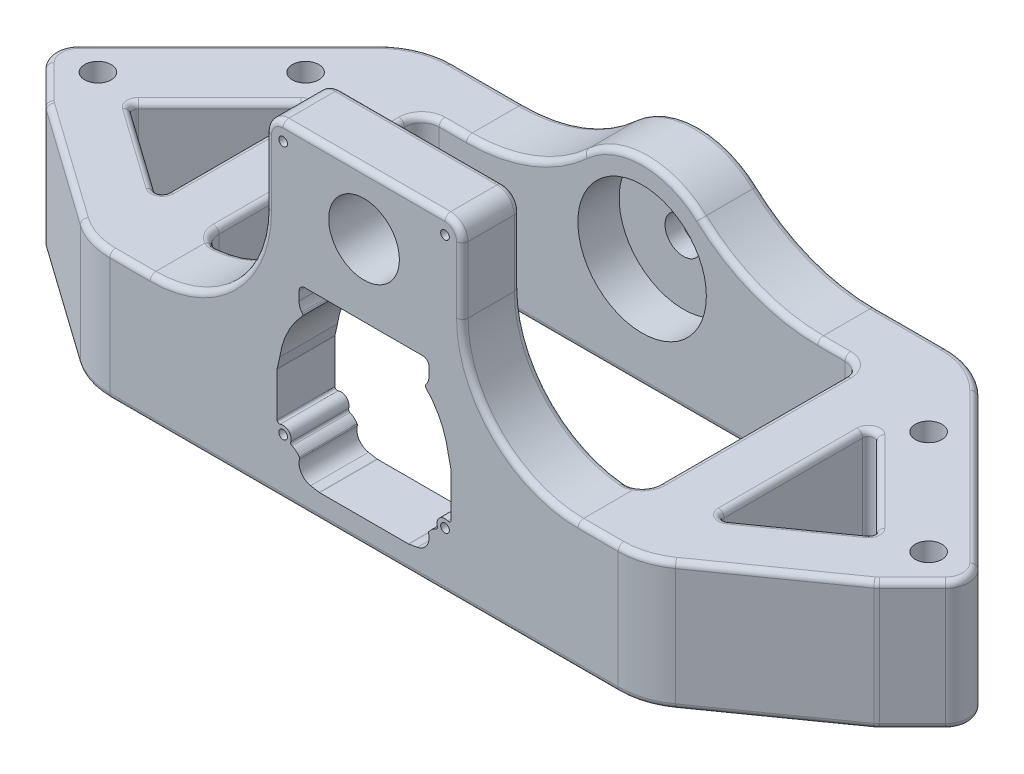
SolidWorks part; units mm, degrees
ref_plane "Front Plane" through (0, 0, 0) normal (0, 0, 1) x (1, 0, 0)
ref_plane "Top Plane" through (0, 0, 0) normal (0, 1, 0) x (1, 0, 0)
ref_plane "Right Plane" through (0, 0, 0) normal (1, 0, 0) x (0, 0, -1)
sketch "Sketch1" plane through (0, 0, 0) normal (0, 1, 0) x (1, 0, 0)
  line L0 (-48.1, -29.05) -> (-48.1, 29.05)
  line L1 (38.1, -19.05) -> (-38.1, -19.05)
  line L2 (38.1, -19.05) -> (38.1, 19.05)
  line L3 (38.1, 19.05) -> (-38.1, 19.05)
  line L4 (-38.1, -19.05) -> (-38.1, 19.05)
  line L5 (38.1, -19.05) -> (-38.1, 19.05) construction
  line L6 (38.1, 19.05) -> (-38.1, -19.05) construction
  line L11 (48.1, 29.05) -> (-48.1, 29.05)
  line L12 (48.1, -29.05) -> (48.1, 29.05)
  line L13 (48.1, -29.05) -> (-48.1, -29.05)
  line L14 (-48.1, 29.05) -> (-80.6068, -3.4568)
  line L15 (-80.6068, -3.4568) -> (-71.842, -12.2215)
  line L16 (-71.842, -12.2215) -> (-48.1, 11.5205)
  line L17 (0, 0) -> (0, 65.6417) construction
  line L18 (-76.3322, -7.7314) -> (0, 68.6008) construction
  line L19 (48.1, 29.05) -> (80.6068, -3.4568)
  line L20 (80.6068, -3.4568) -> (71.842, -12.2215)
  line L21 (71.842, -12.2215) -> (48.1, 11.5205)
  line L22 (-48.1, -29.05) -> (-71.842, -12.2215)
  line L23 (-48.1, -16.7927) -> (-64.669, -5.0485)
  line L24 (48.1, -29.05) -> (71.842, -12.2215)
  line L25 (48.1, -16.7927) -> (64.669, -5.0485)
  line L26 (-76.3322, -7.7314) -> (-269.4077, -200.8069) construction
  circle A0 centre (-71.842, -3.2413) radius 2.3
  circle A1 centre (-53.8815, 14.7193) radius 2.3
  circle A2 centre (53.8815, 14.7193) radius 2.3
  circle A3 centre (71.842, -3.2413) radius 2.3
  point P0 (0, 0)
  point P32 (-197.5656, -128.9648)
  point P34 (-215.5261, -146.9254)
  dimension "D10" = 4.6
  dimension "D1" = 10
  dimension "D2" = 45
  dimension "D3" = 12.3952
  dimension "D4" = 107.95
  dimension "D5" = 6.35
  dimension "D6" = 6.35
  dimension "D7" = 25.4
  dimension "D8" = 76.2
  dimension "D9" = 38.1
  dimension "D11" = 10
  dimension "D12" = 381
  dimension "D13" = 101.6
  dimension "D14" = 177.8
  dimension "D15" = 25.4
  dimension "D16" = 228.6
extrude "Boss-Extrude1" add sketch "Sketch1" along normal blind 22.25 contours L13 L12 L11 L0 L1 L4 L3 L2 | L15 L16 L0 L14 A1 A0 | L21 L20 L19 L12 A2 A3 | L0 L23 L16 L22 | L25 L12 L24 L21 region at (-58.2841, 0, 16.0663) region at (-46.9762, 0, 22.9214) region at (58.2841, 0, 16.0663) region at (-62.2337, 0, -6.6242) region at (62.2337, 0, -6.6242)
extrude "Boss-Extrude2" add sketch "Sketch1<3>" along normal blind 15.85 from surface contours L13 L12 L11 L0 L1 L4 L3 L2 region at (-46.9762, 0, 22.9214) starting at face at (53.623, 22.25, 3.4402)
sketch "Sketch1<3>" plane through (0, 0, 0) normal (0, 1, 0) x (1, 0, 0) same geometry as "Sketch1"
sketch "Sketch3" plane through (0, 0, 29.05) normal (0, 0, 1) x (1, 0, 0)
  line L0 (0, 0) -> (0, 38.1) construction
  line L1 (-48.1, 38.1) -> (48.1, 38.1) construction
  line L2 (7.7467, 4.2612) -> (9.2383, 4.5242)
  line L3 (-7.6773, 4.2551) -> (7.6773, 4.2551)
  line L4 (-9.2383, 4.5242) -> (-7.7467, 4.2612)
  line L5 (-15.0449, 19.0418) -> (-15.0449, 11.4779)
  line L6 (-14.5827, 21.1094) -> (-15.0348, 19.1309)
  line L7 (-10.7806, 29.7585) -> (-10.65, 29.5787)
  line L8 (-6.6626, 32.35) -> (-6.853, 32.6121)
  line L9 (6.853, 32.6121) -> (6.6626, 32.35)
  line L10 (10.65, 29.5787) -> (10.7806, 29.7585)
  line L11 (15.0348, 19.1309) -> (14.5827, 21.1094)
  line L12 (15.0449, 11.4779) -> (15.0449, 19.0418)
  line L13 (-48.1, 22.25) -> (-17, 22.25)
  line L14 (-17, 22.25) -> (-17, 56.7)
  line L15 (-17, 56.7) -> (17, 56.7)
  line L16 (17, 56.7) -> (17, 22.25)
  line L17 (17, 22.25) -> (48.1, 22.25)
  line L18 (48.1, 38.1) -> (48.1, 22.25) construction
  line L19 (48.1, 22.25) -> (48.1, 38.1)
  line L20 (48.1, 38.1) -> (17, 38.1)
  line L21 (-17, 38.1) -> (-48.1, 38.1)
  line L22 (-48.1, 38.1) -> (-48.1, 22.25)
  line L23 (-17, 38.1) -> (17, 38.1)
  line L24 (-11.2442, 31.1853) -> (-11.2442, 33.6774)
  line L25 (-11.2442, 33.6774) -> (11.1927, 33.6774)
  line L26 (11.1927, 33.6774) -> (11.2442, 31.1853)
  circle A0 centre (14, 9.8) radius 0.75
  circle A1 centre (-14, 9.8) radius 0.75
  circle A2 centre (-14, 53.7) radius 0.75
  circle A3 centre (14, 53.7) radius 0.75
  circle A4 centre (0, 46.05) radius 6.114
  arc A5 (12.4458, 8.8644) -> (11.1887, 7.8314) centre (13.5, 6.3) ccw
  arc A6 (9.2383, 4.5242) -> (11.1504, 7.5831) centre (8.8168, 6.9147) ccw
  arc A7 (7.6773, 4.2551) -> (7.7467, 4.2612) centre (7.6773, 4.6551) ccw
  arc A8 (-7.7467, 4.2612) -> (-7.6773, 4.2551) centre (-7.6773, 4.6551) ccw
  arc A9 (-11.1504, 7.5831) -> (-9.2383, 4.5242) centre (-8.8168, 6.9147) ccw
  arc A10 (-11.1887, 7.8314) -> (-12.4458, 8.8644) centre (-13.5, 6.3) ccw
  arc A11 (-12.6734, 9.3602) -> (-14.5014, 11.1045) centre (-14, 9.8) ccw
  arc A12 (-15.0348, 19.1309) -> (-15.0449, 19.0418) centre (-14.6449, 19.0418) ccw
  arc A13 (-10.6753, 29.1957) -> (-14.5827, 21.1094) centre (0, 19.05) ccw
  arc A14 (-6.853, 32.6121) -> (-10.7806, 29.7585) centre (-8.8168, 31.1853) ccw
  arc A15 (6.2909, 32.2555) -> (-6.2909, 32.2555) centre (0, 19.05) ccw
  arc A16 (10.7806, 29.7585) -> (6.853, 32.6121) centre (8.8168, 31.1853) ccw
  arc A17 (14.5827, 21.1094) -> (10.6753, 29.1957) centre (0, 19.05) ccw
  arc A18 (15.0449, 19.0418) -> (15.0348, 19.1309) centre (14.6449, 19.0418) ccw
  arc A19 (14.5014, 11.1045) -> (12.6734, 9.3602) centre (14, 9.8) ccw
  spline S0 degree 3 poles (12.4458, 8.8644) (12.5392, 8.9027) (12.6157, 8.9767) (12.699, 9.1584) (12.7052, 9.2644) (12.6734, 9.3602) knots 0 0 0 0 0.000302 0.000302 0.000604 0.000604 0.000604 0.000604 weights 1 1 1 1 1 1
  spline S1 degree 3 poles (11.1504, 7.5831) (11.1264, 7.6668) (11.1406, 7.7587) (11.1887, 7.8314) knots 0 0 0 0 0.000258 0.000258 0.000258 0.000258 weights 1 1 1 1
  spline S2 degree 3 poles (-11.1887, 7.8314) (-11.1406, 7.7587) (-11.1264, 7.6668) (-11.1504, 7.5831) knots 0 0 0 0 0.000258 0.000258 0.000258 0.000258 weights 1 1 1 1
  spline S3 degree 3 poles (-12.6734, 9.3602) (-12.7052, 9.2644) (-12.699, 9.1582) (-12.6155, 8.9765) (-12.5392, 8.9027) (-12.4458, 8.8644) knots 0 0 0 0 0.000302 0.000302 0.000604 0.000604 0.000604 0.000604 weights 1 1 1 1 1 1
  spline S4 degree 3 poles (-15.0449, 11.4779) (-15.0449, 11.3476) (-14.9779, 11.2213) (-14.7643, 11.0748) (-14.6231, 11.0578) (-14.5014, 11.1045) knots 0 0 0 0 0.000388 0.000388 0.000776 0.000776 0.000776 0.000776 weights 1 1 1 1 1 1
  spline S5 degree 3 poles (-10.65, 29.5787) (-10.6088, 29.522) (-10.5888, 29.4526) (-10.5979, 29.3131) (-10.627, 29.2466) (-10.6753, 29.1957) knots 0 0 0 0 0.000207 0.000207 0.000415 0.000415 0.000415 0.000415 weights 1 1 1 1 1 1
  spline S6 degree 3 poles (-6.2909, 32.2555) (-6.3541, 32.2254) (-6.4259, 32.2184) (-6.5613, 32.2528) (-6.6214, 32.2934) (-6.6626, 32.35) knots 0 0 0 0 0.000207 0.000207 0.000414 0.000414 0.000414 0.000414 weights 1 1 1 1 1 1
  spline S7 degree 3 poles (6.6626, 32.35) (6.6214, 32.2934) (6.5617, 32.2529) (6.4263, 32.2184) (6.3541, 32.2254) (6.2909, 32.2555) knots 0 0 0 0 0.000207 0.000207 0.000414 0.000414 0.000414 0.000414 weights 1 1 1 1 1 1
  spline S8 degree 3 poles (10.6753, 29.1957) (10.627, 29.2466) (10.598, 29.3127) (10.5887, 29.4522) (10.6088, 29.522) (10.65, 29.5787) knots 0 0 0 0 0.000207 0.000207 0.000415 0.000415 0.000415 0.000415 weights 1 1 1 1 1 1
  spline S9 degree 3 poles (14.5014, 11.1045) (14.6231, 11.0578) (14.765, 11.075) (14.9783, 11.2218) (15.0449, 11.3476) (15.0449, 11.4779) knots 0 0 0 0 0.000388 0.000388 0.000776 0.000776 0.000776 0.000776 weights 1 1 1 1 1 1
  point P5 (0, 19.05)
  point P17 (0, 19.05)
  point P86 (0, 33.6774)
  line M46 (48.1, 22.25) -> (48.1, 38.1)
  line M47 (48.1, 38.1) -> (-48.1, 38.1)
  line M48 (-48.1, 38.1) -> (-48.1, 22.25)
  dimension "D1" = 1.5
  dimension "D2" = 3
  dimension "D3" = 3
  dimension "D4" = 3
extrude "Boss-Extrude3" add sketch "Sketch3" against normal up to surface (10 mm away) contours L16 L15 L14 L23 A4 A3 A2 M47 region at (-16.6124, 47.4, 29.05) up to face at (0, 19.05, 19.05)
extrude "Cut-Extrude1" cut sketch "Sketch3<3>" against normal up to next contours L13 L14 M47 M48 | L16 L17 M46 M47 region at (-32.55, 30.175, 29.05) region at (32.55, 30.175, 29.05)
sketch "Sketch3<3>" plane through (0, 0, 29.05) normal (0, 0, 1) x (1, 0, 0) same geometry as "Sketch3"
extrude "Cut-Extrude2" cut sketch "Sketch3<4>" against normal up to next contours L3 L0 A15 S6 L8 A14 L7 S5 A13 L6 A12 L5 S4 A11 S3 A10 S2 A9 L4 A8 | L0 L3 A7 L2 A6 S1 A5 S0 A19 S9 L12 A18 L11 A17 S8 L10 A16 L9 S7 A15 | A1 | A0 | S6 A15 L25 L24 A14 L8 | S7 L9 A16 L26 L25 A15 region at (-6.6584, 18.6234, 29.05) region at (6.6584, 18.6234, 29.05) region at (-6.742, 33.2078, 29.05) region at (6.692, 33.2118, 29.05) region at (14, 9.8, 29.05) region at (-14, 9.8, 29.05)
sketch "Sketch3<4>" plane through (0, 0, 29.05) normal (0, 0, 1) x (1, 0, 0) same geometry as "Sketch3"
sketch "Sketch4" plane through (0, 0, -29.05) normal (0, 0, -1) x (-1, 0, 0)
  line L0 (0, 0) -> (0, 38.1) construction
  line L1 (17, 38.1) -> (-17, 38.1) construction
  line L5 (-17, 22.25) -> (-14.6547, 22.25)
  line L6 (-17, 22.25) -> (-17, 38.1)
  line L7 (-17, 38.1) -> (17, 38.1)
  line L8 (17, 38.1) -> (17, 22.25)
  line L9 (17, 22.25) -> (14.6547, 22.25)
  circle A0 centre (0, 19.05) radius 3.175
  circle A1 centre (0, 19.05) radius 15
  line M7 (17, 22.25) -> (17, 38.1)
  line M8 (17, 38.1) -> (-17, 38.1)
  line M9 (-17, 38.1) -> (-17, 22.25)
  dimension "D1" = 30
  dimension "D2" = 6.35
extrude "Cut-Extrude3" cut sketch "Sketch4" against normal up to next contours A1 L0 L7 L5 M9 | L0 A1 L9 M7 M8 | L0 A0 | A0 L0 region at (1.3475, 19.05, -29.05) region at (-1.3475, 19.05, -29.05) region at (10.8276, 32.9317, -29.05) region at (-10.8276, 32.9317, -29.05)
fillet "Fillet1" radius 20 2 edges at (17, 22.25, 24.05) (-17, 22.25, 24.05)
fillet "Fillet2" radius 3 2 edges at (-17, 56.7, 24.05) (17, 56.7, 24.05)
fillet "Fillet3" radius 1 2 edges at (11.1927, 33.6774, 24.05) (-11.2442, 33.6774, 24.05)
fillet "Fillet4" radius 1 6 edges at (48.1, 11.125, -11.5205) (-48.1, 11.125, -11.5205) (48.1, 11.125, 16.7927) (64.669, 11.125, 5.0485) (-48.1, 11.125, 16.7927) (-64.669, 11.125, 5.0485)
fillet "Fillet5" radius 3 4 edges at (-38.1, 11.125, -19.05) (38.1, 11.125, -19.05) (38.1, 11.125, 19.05) (-38.1, 11.125, 19.05)
fillet "Fillet6" radius 13 4 edges at (48.1, 11.125, -29.05) (-48.1, 11.125, -29.05) (-48.1, 11.125, 29.05) (48.1, 11.125, 29.05)
fillet "Fillet7" radius 4 4 edges at (80.6068, 11.125, 3.4568) (-80.6068, 11.125, 3.4568) (71.842, 11.125, 12.2215) (-71.842, 11.125, 12.2215)
sketch "Sketch5" plane through (0, 0, -19.05) normal (0, 0, 1) x (1, 0, 0)
  circle A0 centre (0, 19.05) radius 11.1125
  dimension "D1" = 22.225
extrude "Cut-Extrude4" cut sketch "Sketch5" against normal blind 7.1374
fillet "Fillet8" radius 30 2 edges at (14.6547, 22.25, -24.05) (-14.6547, 22.25, -24.05)
fillet "Fillet9" radius 1 8 edges at (56.8192, 0, -2.8014) (56.8192, 22.25, -2.8014) (-48.1, 22.25, 2.8759) (-48.1, 0, 2.8759) (-38.1, 0, 0) (-22.2014, 28.7964, 19.05) (0, 0, -29.05) (-64.843, 22.25, -12.307)
